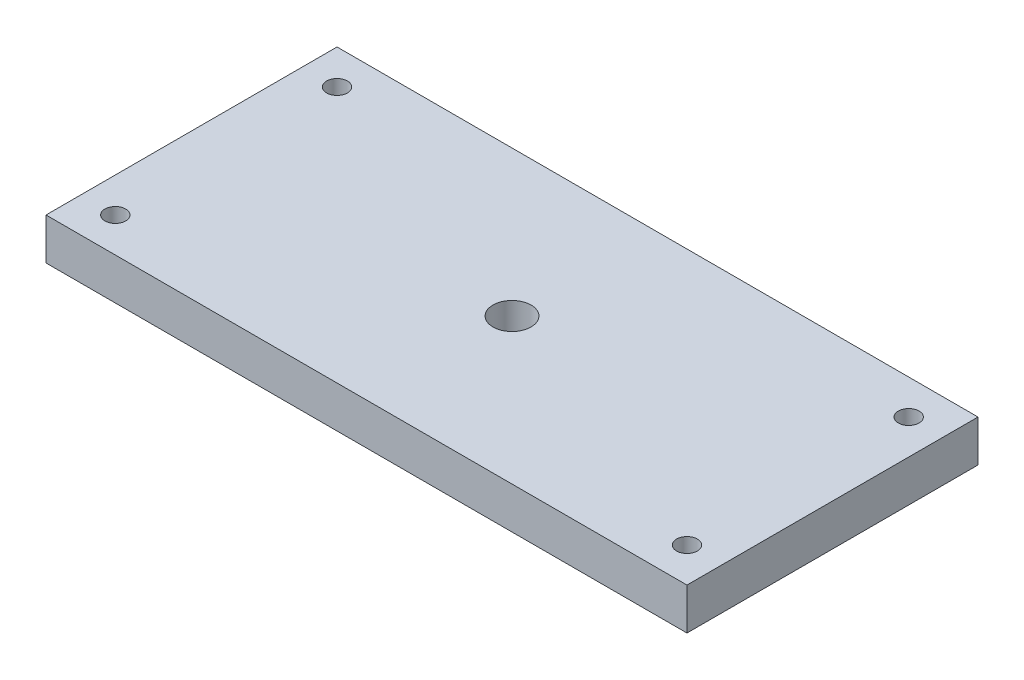
SolidWorks part; units mm, degrees
ref_plane "Płaszczyzna przednia" through (0, 0, 0) normal (0, 0, 1) x (1, 0, 0)
ref_plane "Płaszczyzna górna" through (0, 0, 0) normal (0, 1, 0) x (1, 0, 0)
ref_plane "Płaszczyzna prawa" through (0, 0, 0) normal (1, 0, 0) x (0, 0, -1)
sketch "Sketch2" plane through (0, 0, 0) normal (0, 1, 0) x (1, 0, 0)
  line L0 (-25.9967, 13.7153) -> (66.5033, 13.7153) construction
  line L1 (-25.9967, 34.7153) -> (66.5033, 34.7153)
  line L2 (-25.9967, 34.7153) -> (-25.9967, -7.2847)
  line L3 (-25.9967, -7.2847) -> (66.5033, -7.2847)
  line L4 (66.5033, 34.7153) -> (66.5033, -7.2847)
  line L5 (20.2533, 34.7153) -> (20.2533, -7.2847) construction
  circle A0 centre (-20.9967, 29.7153) radius 1.5
  circle A1 centre (-20.9967, -2.2847) radius 1.5
  circle A2 centre (61.5033, -2.2847) radius 1.5
  circle A3 centre (61.5033, 29.7153) radius 1.5
  circle A4 centre (20.2533, 13.7153) radius 2.75
  dimension "D1" = 3
  dimension "D6" = 5.5
  dimension "D2" = 32
  dimension "D3" = 82.5
  dimension "D4" = 5
  dimension "D5" = 5
extrude "Boss-Extrude1" add sketch "Sketch2" along normal blind 6
